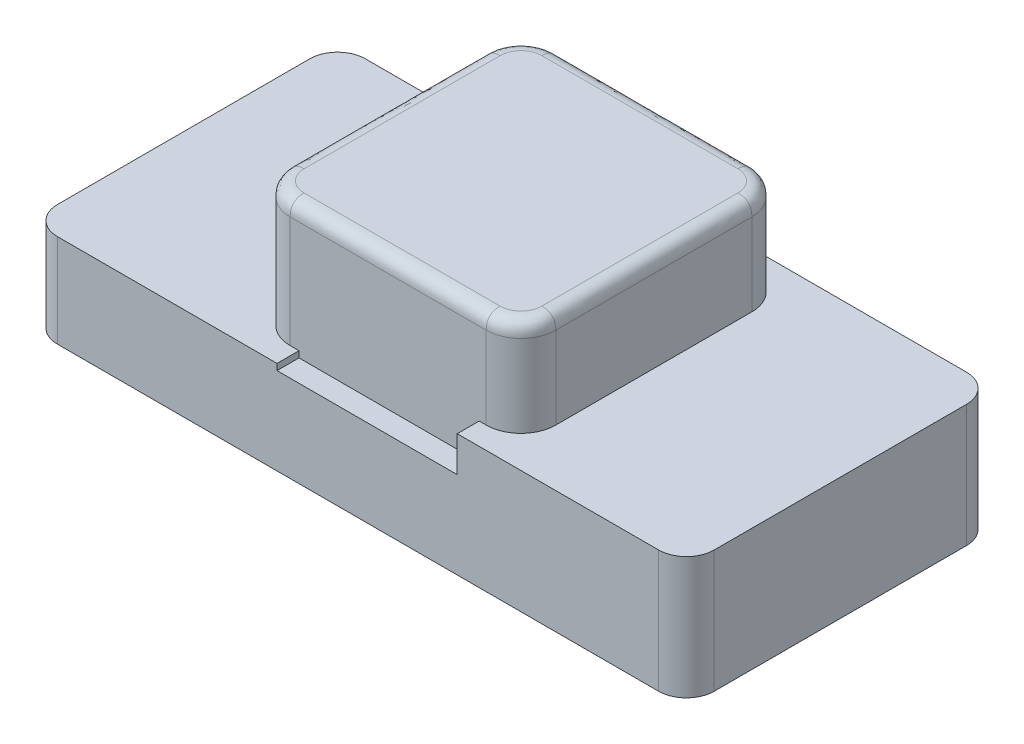
SolidWorks part; units mm, degrees
ref_plane "Front Plane" through (0, 0, 0) normal (0, 0, 1) x (1, 0, 0)
ref_plane "Top Plane" through (0, 0, 0) normal (0, 1, 0) x (1, 0, 0)
ref_plane "Right Plane" through (0, 0, 0) normal (1, 0, 0) x (0, 0, -1)
sketch "Sketch1" plane through (0, 0, 0) normal (0, 1, 0) x (1, 0, 0)
  line L0 (-11.65, -22.145) -> (-11.65, -18.985)
  line L1 (-43.23, -22.145) -> (43.23, -22.145)
  line L2 (-47.23, -18.145) -> (-47.23, 18.145)
  line L3 (-43.23, 22.145) -> (43.23, 22.145)
  line L4 (47.23, -18.145) -> (47.23, 18.145)
  line L5 (-47.23, -22.145) -> (47.23, 22.145) construction
  line L6 (-47.23, 22.145) -> (47.23, -22.145) construction
  line L7 (-12.92, 19.215) -> (15.28, 19.215)
  line L8 (-17.92, 14.215) -> (-17.92, -13.985)
  line L9 (-12.92, -18.985) -> (15.28, -18.985)
  line L10 (20.28, 14.215) -> (20.28, -13.985)
  line L11 (-11.65, 19.215) -> (-11.65, 22.145)
  line L12 (14.27, -18.985) -> (14.27, -22.145)
  line L13 (14.27, 19.215) -> (14.27, 22.145)
  arc A0 (-43.23, -22.145) -> (-47.23, -18.145) centre (-43.23, -18.145) cw
  arc A1 (47.23, 18.145) -> (43.23, 22.145) centre (43.23, 18.145) ccw
  arc A2 (47.23, -18.145) -> (43.23, -22.145) centre (43.23, -18.145) cw
  arc A3 (-43.23, 22.145) -> (-47.23, 18.145) centre (-43.23, 18.145) ccw
  arc A4 (20.28, -13.985) -> (15.28, -18.985) centre (15.28, -13.985) cw
  arc A5 (-17.92, 14.215) -> (-12.92, 19.215) centre (-12.92, 14.215) cw
  arc A6 (15.28, 19.215) -> (20.28, 14.215) centre (15.28, 14.215) cw
  arc A7 (-12.92, -18.985) -> (-17.92, -13.985) centre (-12.92, -13.985) cw
  point P0 (0, 0)
  point P32 (20.28, -18.985)
  point P37 (20.28, 19.215)
  point P40 (-17.92, -18.985)
  dimension "D11" = 4
  dimension "D12" = 5
  dimension "D1" = 94.46
  dimension "D2" = 44.29
  dimension "D3" = 38.2
  dimension "D4" = 38.2
  dimension "D5" = 3.16
  dimension "D6" = 2.93
  dimension "D7" = 29.31
  dimension "D8" = 26.95
  dimension "D9" = 35.58
  dimension "D10" = 32.96
extrude "Boss-Extrude1" add sketch "Sketch1" along normal blind 31.42 contours L10 L7 L8 L9 region at (1.18, 0, -0.115)
extrude "Boss-Extrude2" add sketch "Sketch1<3>" along normal blind 13.4 contours L7 L11 L3 L2 L1 L0 L9 L8 region at (-31.8713, 0, 0.0196)
sketch "Sketch1<3>" plane through (0, 0, 0) normal (0, 1, 0) x (1, 0, 0) same geometry as "Sketch1"
extrude "Boss-Extrude3" add sketch "Sketch1<4>" along normal blind 17.6 contours L13 L7 L10 L9 L12 L1 L4 L3 region at (33.0693, 0, 0.0204)
sketch "Sketch1<4>" plane through (0, 0, 0) normal (0, 1, 0) x (1, 0, 0) same geometry as "Sketch1"
extrude "Boss-Extrude4" add sketch "Sketch1<5>" along normal blind 12.5 contours L12 L9 L0 L1 | L7 L13 L3 L11 region at (1.31, 0, 20.565) region at (1.31, 0, -20.68)
sketch "Sketch1<5>" plane through (0, 0, 0) normal (0, 1, 0) x (1, 0, 0) same geometry as "Sketch1"
fillet "Fillet2" radius 2 8 edges at (-17.92, 31.42, -0.115) (-16.4555, 31.42, -17.7505) (1.18, 31.42, -19.215) (18.8155, 31.42, -17.7505) (20.28, 31.42, -0.115) (18.8155, 31.42, 17.5205) (1.18, 31.42, 18.985) (-16.4555, 31.42, 17.5205) conic rho 0.5
